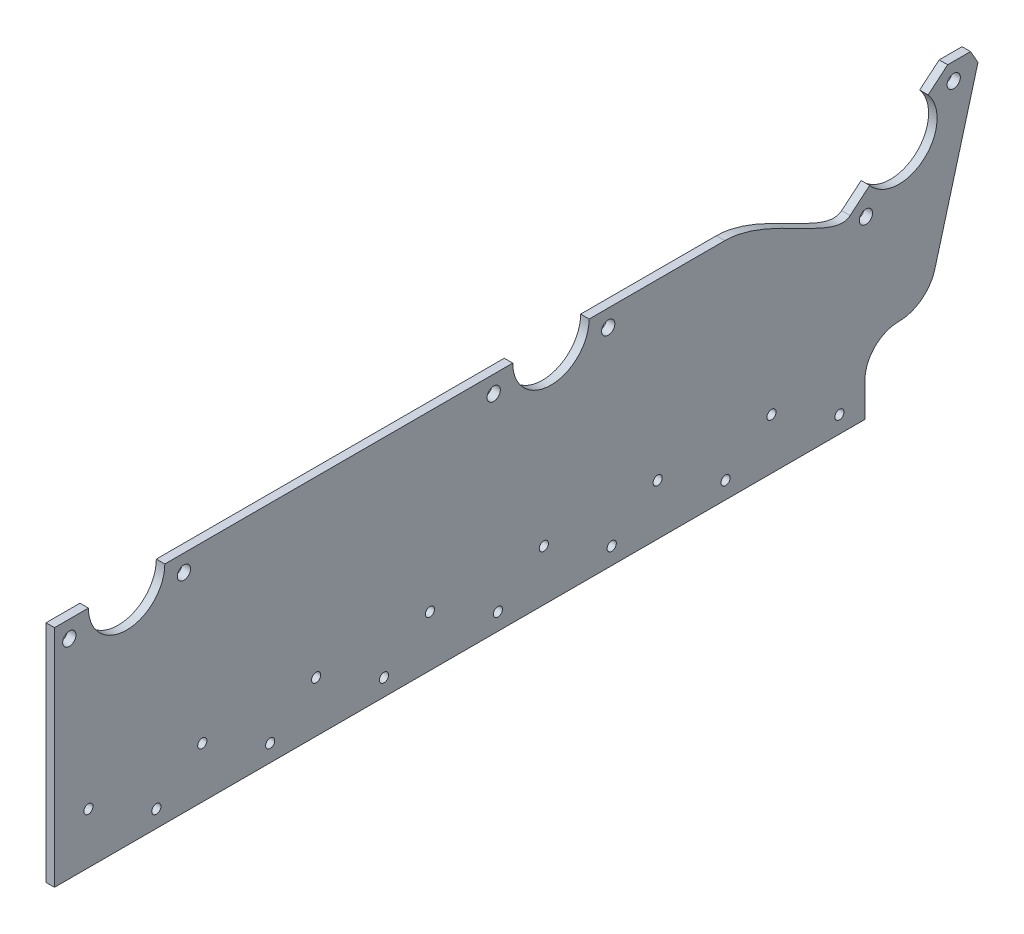
SolidWorks part; units mm, degrees
material "6061 Alloy"
ref_plane "Front Plane" through (0, 0, 0) normal (0, 0, 1) x (1, 0, 0)
ref_plane "Top Plane" through (0, 0, 0) normal (0, 1, 0) x (1, 0, 0)
ref_plane "Right Plane" through (0, 0, 0) normal (1, 0, 0) x (0, 0, -1)
sketch "Sketch1" plane through (0, 0, 0) normal (1, 0, 0) x (0, 0, -1)
  line L0 (-12.7, -12.7) -> (-315.9125, -12.7)
  line L1 (-315.9125, -12.7) -> (-315.9125, 71.4375)
  line L2 (-315.9125, 71.4375) -> (-303.2125, 71.4375)
  line L3 (-274.6375, 71.4375) -> (-144.4625, 71.4375)
  line L5 (10.9449, 80.6213) -> (18.2432, 86.7453)
  line L7 (-315.9125, 12.7) -> (13.4735, 12.7) construction
  line L8 (-12.7, -12.7) -> (-12.7, 0)
  line L9 (0, 12.4079) -> (0, 12.7) construction
  line L10 (13.4735, 22.9788) -> (30.9432, 86.7453)
  line L12 (-10.9449, 62.2537) -> (10.9449, 80.6213) construction
  line L13 (18.2432, 86.7453) -> (30.9432, 86.7453)
  line L14 (-115.8875, 71.4375) -> (-65.0875, 71.4375)
  line L15 (-10.9449, 62.2537) -> (-18.2432, 56.1297)
  line L16 (-315.9125, 15.875) -> (13.4735, 15.875) construction
  line L18 (0, 71.4375) -> (-130.175, 71.4375) construction
  arc A3 (0, 12.7) -> (13.4735, 22.9788) centre (0, 26.67) ccw
  arc A4 (0, 12.7) -> (-12.7, 0) centre (0, 0) ccw
  circle A5 centre (0, 0) radius 12.4079 construction
  arc A6 (-303.2125, 71.4375) -> (-274.6375, 71.4375) centre (-288.925, 71.4375) ccw
  arc A7 (-144.4625, 71.4375) -> (-115.8875, 71.4375) centre (-130.175, 71.4375) ccw
  arc A8 (-10.9449, 62.2537) -> (10.9449, 80.6213) centre (0, 71.4375) ccw
  spline S0 degree 3 poles (-18.2432, 56.1297) (-24.729, 50.6874) (-48.1542, 71.4375) (-65.0875, 71.4375) knots 0 0 0 0 1 1 1 1
  point P4 (-164.3062, -12.7)
  dimension "D1" = 25.4
  dimension "D3" = 12.7
  dimension "D5" = 28.575
  dimension "D6" = 41.275
  dimension "D7" = 13.97
  dimension "D8" = 12.7
  dimension "D10" = 24.8158
  dimension "D13" = 9.5273
  dimension "D14" = 140
  dimension "D15" = 50.8
  dimension "D16" = 50.8
  dimension "D17" = 25.4
  dimension "D2" = 0
  dimension "D4" = 12.7
  dimension "D9" = 12.7
  dimension "D11" = 288.925
  dimension "D12" = 288.925
  dimension "D18" = 3.175
extrude "Boss-Extrude1" add sketch "Sketch1" along normal blind 3.175
hole_wizard "#10 Clearance Hole1" positions "Sketch2" profile "Sketch3" hole size "#10" standard "ANSI Inch" end condition through all
sketch "Sketch2" plane through (3.175, 0, 0) normal (1, 0, 0) x (0, 0, -1)
  line L0 (-310.3562, 65.0875) -> (-267.4937, 65.0875) construction
  line L2 (-151.6062, 65.0875) -> (-108.7437, 65.0875) construction
  line L4 (-12.3356, 52.7974) -> (20.499, 80.3489) construction
  line L6 (-303.2125, 71.4375) -> (-315.9125, 71.4375) construction
  line L7 (-288.925, 65.0875) -> (-288.925, 71.4375) construction
  line L9 (-130.175, 71.4375) -> (-130.175, 65.0875) construction
  line L11 (0, 71.4375) -> (4.0817, 66.5731) construction
  line L14 (18.2432, 86.7453) -> (10.9449, 80.6213) construction
  line L15 (18.2432, 86.7453) -> (10.9449, 80.6213) construction
  point P0 (-310.3562, 65.0875)
  point P2 (-267.4937, 65.0875)
  point P4 (-151.6062, 65.0875)
  point P6 (-108.7437, 65.0875)
  point P8 (-12.3356, 52.7974)
  point P10 (20.499, 80.3489)
  dimension "D1" = 42.8625
  dimension "D2" = 6.35
  dimension "D3" = 6.35
sketch "Sketch3" plane through (3.175, 65.0875, 310.3562) normal (0, 1, 0) x (0, 0, -1)
  line L0 (0, 0) -> (0, 3.175)
  line L1 (0, 3.175) -> (2.4892, 3.175)
  line L2 (2.4892, 3.175) -> (2.4892, 0)
  line L5 (2.4892, 0) -> (0, 0)
  line L11 (0, -6.35) -> (0, 107.95) construction
  dimension "Thru Hole Dia." = 4.9784
  dimension "Thru Hole Depth" = 3.175
chamfer "Chamfer1" distance 5.08 angle 45 1 edges at (1.5875, 86.7453, -30.9432) first distance on face at (1.5875, 54.862, -22.2083)
hole_wizard "1/8 (0.135) Diameter Hole1" positions "Sketch4" profile "Sketch5" hole size "1/8" standard "ANSI Inch"
sketch "Sketch4" plane through (3.175, 0, 0) normal (1, 0, 0) x (0, 0, -1)
  line L0 (-315.9125, -12.7) -> (-12.7, -12.7) construction
  line L1 (-12.7, -12.7) -> (-12.7, 0) construction
  line L2 (-315.9125, 71.4375) -> (-315.9125, -12.7) construction
  point P0 (-22.2504, -6.35)
  point P2 (-47.6504, 6.35)
  point P14 (-64.8441, -6.35)
  point P15 (-90.2441, 6.35)
  point P16 (-107.4378, -6.35)
  point P17 (-132.8378, 6.35)
  point P18 (-150.0314, -6.35)
  point P19 (-175.4315, 6.35)
  point P20 (-192.6251, -6.35)
  point P21 (-218.0251, 6.35)
  point P22 (-235.2188, -6.35)
  point P23 (-260.6188, 6.35)
  point P24 (-277.8125, -6.35)
  point P25 (-303.2125, 6.35)
  dimension "D1" = 6.35
  dimension "D2" = 9.5504
  dimension "D3" = 12.7
  dimension "D4" = 25.4
  dimension "D6" = 12.7
  dimension "D5" = 7
sketch "Sketch5" plane through (3.175, -6.35, 22.2504) normal (0, 1, 0) x (0, 0, -1)
  line L0 (0, 0) -> (0, 17.5402)
  line L1 (0, 17.5402) -> (1.7145, 16.51)
  line L2 (1.7145, 16.51) -> (1.7145, 0)
  line L5 (1.7145, 0) -> (0, 0)
  line L10 (0, 17.5402) -> (-1.7145, 16.51) construction
  line L11 (0, -6.35) -> (0, 107.95) construction
  dimension "Hole Dia." = 3.429
  dimension "Hole Depth" = 16.51
  dimension "Drill Angle" = 118
